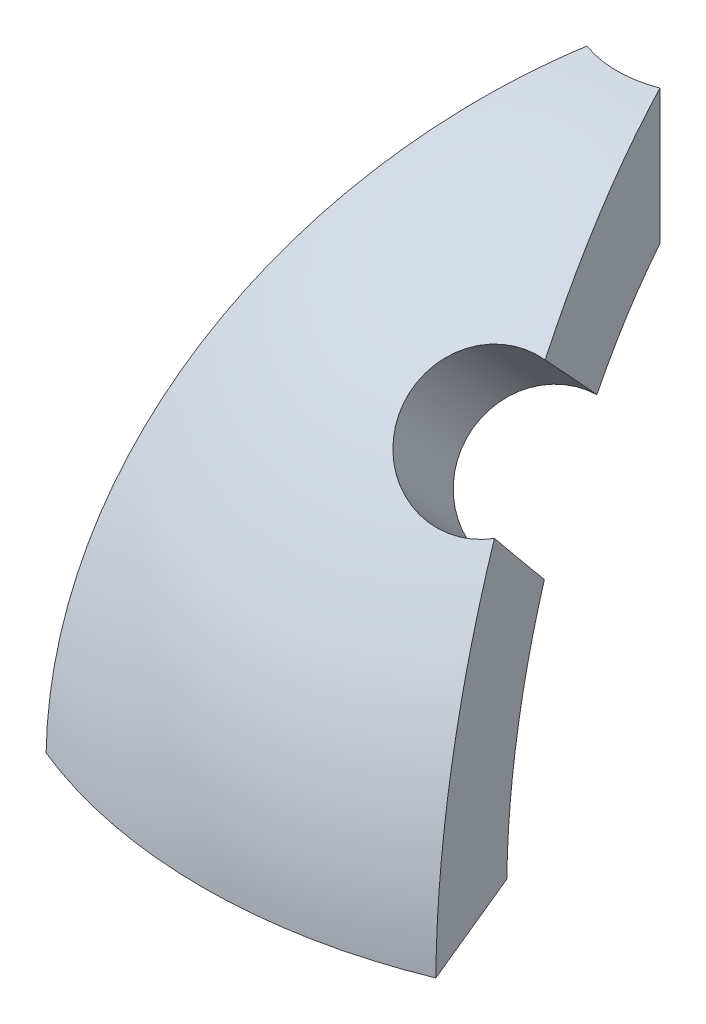
SolidWorks part; units mm, degrees
ref_plane "Front Plane" through (0, 0, 0) normal (0, 0, 1) x (1, 0, 0)
ref_plane "Top Plane" through (0, 0, 0) normal (0, 1, 0) x (1, 0, 0)
ref_plane "Right Plane" through (0, 0, 0) normal (1, 0, 0) x (0, 0, -1)
sketch "Sketch1" plane through (0, 0, 0) normal (1, 0, 0) x (0, 0, -1)
  line L1 (19.05, 0) -> (-19.05, 0) construction
  line L2 (-3.81, 13.4404) -> (-3.81, 9.4186) construction
  line L3 (-14.2178, 0.25) -> (-19.0484, 0.25)
  line L4 (-3.81, 18.6651) -> (-3.81, 13.7001)
  line L5 (0, 0) -> (0, 50000) construction
  arc A0 (-3.81, 13.4404) -> (-13.97, 0) centre (0, 0) ccw construction
  arc A1 (-3.81, 13.4404) -> (-13.97, 0) centre (0, 0) ccw construction
  arc A2 (-3.81, 13.7001) -> (-14.2178, 0.25) centre (0, 0) ccw
  arc A3 (-2.4953, 13.7453) -> (-13.97, 0) centre (0, 0) ccw construction
  arc A4 (-3.81, 18.6651) -> (-19.0484, 0.25) centre (0, 0) ccw
  arc A5 (-2.54, 13.9913) -> (-14.22, 0) centre (0, 0) ccw construction
  arc A6 (-19.05, 0) -> (19.05, 0) centre (0, 0) ccw construction
  dimension "D2" = 0.25
  dimension "D1" = 0.25
revolve "Revolve1" add sketch "Sketch1" angle 45 mid plane about L5
sketch "Sketch2" plane through (0, 0, 0) normal (0, 1, 0) x (1, 0, 0)
  line L0 (7.2895, -17.5984) -> (1.458, -3.52) construction
  line L1 (7.2895, -17.5984) -> (1.458, -3.52)
  line L2 (7.1738, -17.6458) -> (1.3418, -3.5659)
  line L3 (7.174, -17.6462) -> (1.3425, -3.5678) construction
  line L4 (0, 0) -> (0, -50000) construction
  line L5 (-7.1738, -17.6458) -> (-1.3418, -3.5659)
  line L6 (-7.2895, -17.5984) -> (-1.458, -3.52)
  arc A0 (-7.2895, -17.5984) -> (7.2895, -17.5984) centre (0, 0) ccw construction
  arc A1 (-1.458, -3.52) -> (1.458, -3.52) centre (0, 0) ccw construction
  arc A2 (7.1738, -17.6458) -> (7.2895, -17.5984) centre (0, 0) ccw
  arc A3 (1.3418, -3.5659) -> (1.458, -3.52) centre (0, 0) ccw
  arc A4 (-1.3418, -3.5659) -> (-1.458, -3.52) centre (0, 0) cw
  arc A5 (-7.1738, -17.6458) -> (-7.2895, -17.5984) centre (0, 0) cw
  dimension "D1" = 0.125
extrude "Cut-Extrude1" cut sketch "Sketch2" against normal through all both and the other way through all
ref_plane "Plane1" through (0, 0, 0) normal (0, 0.7071, 0.7071) x (-1, 0, 0)
ref_plane "Plane2" through (0, 0, 0) normal (0, 0.3827, 0.9239) x (-1, 0, 0)
sketch "Sketch8" plane through (0, 0, 0) normal (0, 0.3827, 0.9239) x (-1, 0, 0)
  line L0 (-18.6381, 3.9399) -> (18.6381, 3.9399) construction
  arc A0 (19.05, 0) -> (-19.05, 0) centre (0, 0) ccw construction
  ellipse E0 centre (0, -0.231) end of major axis (14.2178, -0.231) minor radius 5.4409 (5.3252, 4.8139) -> (-5.3252, 4.8139) ccw construction
  ellipse E1 centre (0, -0.231) end of major axis (14.2178, -0.231) minor radius 5.4409 (5.3252, 4.8139) -> (-5.3252, 4.8139) ccw construction
  text T0 "<r180>    7</r>" font "Century Gothic" height 4.445
  point P3 (0, 3.9399)
  dimension "D1" = 2.54
extrude "Cut-Extrude4" cut sketch "Sketch8" along normal blind 0.381 from surface starting at face at (0, 7.8389, 9.7254)
ref_plane "Plane3" through (8.5616, 18.8585, 16.8031) normal (0.321, 0.7071, 0.63) x (0.9471, -0.2397, -0.2136)
sketch "Sketch9" plane through (5.8276, 18.8585, 17.9355) normal (-0.2185, -0.7071, -0.6725) x (-0.8207, -0.2397, 0.5187)
  circle A0 centre (0, 0) radius 2.54 construction
  circle A1 centre (0, 0) radius 2.54 construction
  circle A2 centre (0, 0) radius 2.6035
  dimension "D1" = 5.207
extrude "Cut-Extrude5" cut sketch "Sketch9" against normal through all both and the other way through all
